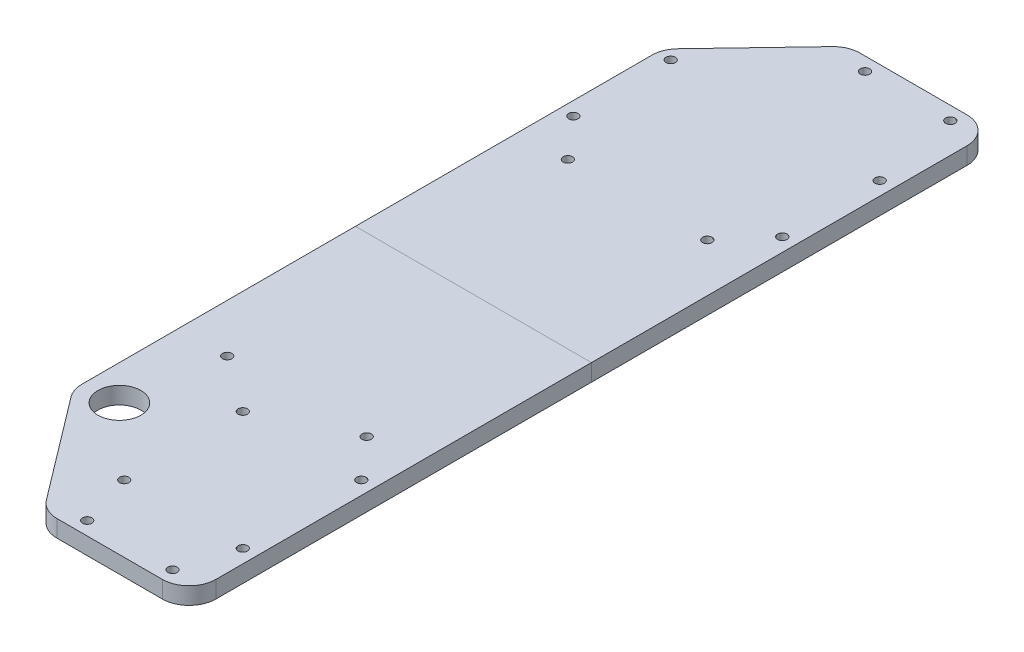
SolidWorks part; units mm, degrees
ref_plane "Front Plane" through (0, 0, 0) normal (0, 0, 1) x (1, 0, 0)
ref_plane "Top Plane" through (0, 0, 0) normal (0, 1, 0) x (1, 0, 0)
ref_plane "Right Plane" through (0, 0, 0) normal (1, 0, 0) x (0, 0, -1)
sketch "Sketch1" plane through (0, 0, 0) normal (0, 1, 0) x (1, 0, 0)
  line L0 (45, 295) -> (76.8, 295) construction
  line L1 (0, 0) -> (88, 0)
  line L2 (0, 0) -> (0, 300)
  line L3 (0, 300) -> (88, 300)
  line L4 (88, 0) -> (88, 300)
  line L5 (18, 211.2) -> (70, 211.2) construction
  line L6 (18, 211.2) -> (18, 84.2) construction
  line L7 (18, 84.2) -> (70, 84.2) construction
  line L8 (70, 211.2) -> (70, 84.2) construction
  line L9 (38.8, 69.2) -> (83, 69.2) construction
  line L10 (38.8, 69.2) -> (38.8, 25) construction
  line L11 (38.8, 25) -> (83, 25) construction
  line L12 (83, 69.2) -> (83, 25) construction
  line L13 (5.05, 226.2) -> (82.95, 226.2) construction
  line L14 (5.05, 226.2) -> (5.05, 262.5) construction
  line L15 (5.05, 262.5) -> (82.95, 262.5) construction
  line L16 (82.95, 226.2) -> (82.95, 262.5) construction
  line L17 (45, 5) -> (76.8, 5) construction
  line L18 (38.8, 25) -> (45, 5) construction
  line L19 (76.8, 5) -> (83, 25) construction
  line L20 (33.8, 0) -> (0, 44.6331)
  line L21 (33.8, 300) -> (0, 264.5204)
  line L22 (13, 49) -> (0, 49) construction
  line L23 (13, 49) -> (2.6364, 41.1518) construction
  line L24 (5.05, 262.5) -> (0, 262.5) construction
  line L25 (5.05, 262.5) -> (1.3936, 265.9833) construction
  circle A0 centre (18, 211.2) radius 1.75
  circle A1 centre (70, 84.2) radius 1.75
  circle A2 centre (18, 84.2) radius 1.75
  circle A3 centre (70, 211.2) radius 1.75
  circle A4 centre (5.05, 262.5) radius 1.75
  circle A5 centre (5.05, 226.2) radius 1.75
  circle A6 centre (82.95, 226.2) radius 1.75
  circle A7 centre (82.95, 262.5) radius 1.75
  circle A8 centre (38.8, 69.2) radius 1.75
  circle A9 centre (83, 69.2) radius 1.75
  circle A10 centre (83, 25) radius 1.75
  circle A11 centre (38.8, 25) radius 1.75
  circle A12 centre (45, 295) radius 1.75
  circle A13 centre (76.8, 295) radius 1.75
  circle A14 centre (45, 5) radius 1.75
  circle A15 centre (76.8, 5) radius 1.75
  circle A16 centre (13, 49) radius 8
  dimension "D3" = 3.5
  dimension "D14" = 3.5
  dimension "D21" = 16
  dimension "D1" = 88
  dimension "D2" = 300
  dimension "D4" = 52
  dimension "D5" = 127
  dimension "D6" = 18
  dimension "D7" = 77.9
  dimension "D8" = 36.3
  dimension "D9" = 44.2
  dimension "D11" = 5.05
  dimension "D12" = 15
  dimension "D13" = 15
  dimension "D10" = 5
  dimension "D15" = 5
  dimension "D16" = 11.2
  dimension "D18" = 5
  dimension "D17" = 31.8
  dimension "D19" = 11.2
  dimension "D20" = 20
  dimension "D22" = 13
  dimension "D23" = 49
  dimension "D24" = 11.2
  dimension "D25" = 11.2
extrude "Boss-Extrude1" add sketch "Sketch1" along normal blind 6.35 contours L20 L1 L4 L3 L2 A16 A15 A14 A13 A12 A11 A10 A9 A8 A7 A6 A5 A4 A3 A2 A1 A0 region at (45.9946, 0, -151.6118)
fillet "Fillet1" radius 10 6 edges at (88, 3.175, -300) (88, 3.175, 0) (33.8, 3.175, 0) (0, 3.175, -44.6331) (33.8, 3.175, -300) (0, 3.175, -264.5204)
ref_plane "Plane1" through (0, 0, -150) normal (0, 0, 1) x (1, 0, 0)
split "Split1" trim tools "Plane1" bodies to split 104 resulting bodies 105 106
equation "\"D16@Sketch1\"=\"D19@Sketch1\""
equation "\"D24@Sketch1\"=\"D19@Sketch1\""
equation "\"D13@Sketch1\"=\"D12@Sketch1\""
equation "\"D25@Sketch1\"=\"D19@Sketch1\""
